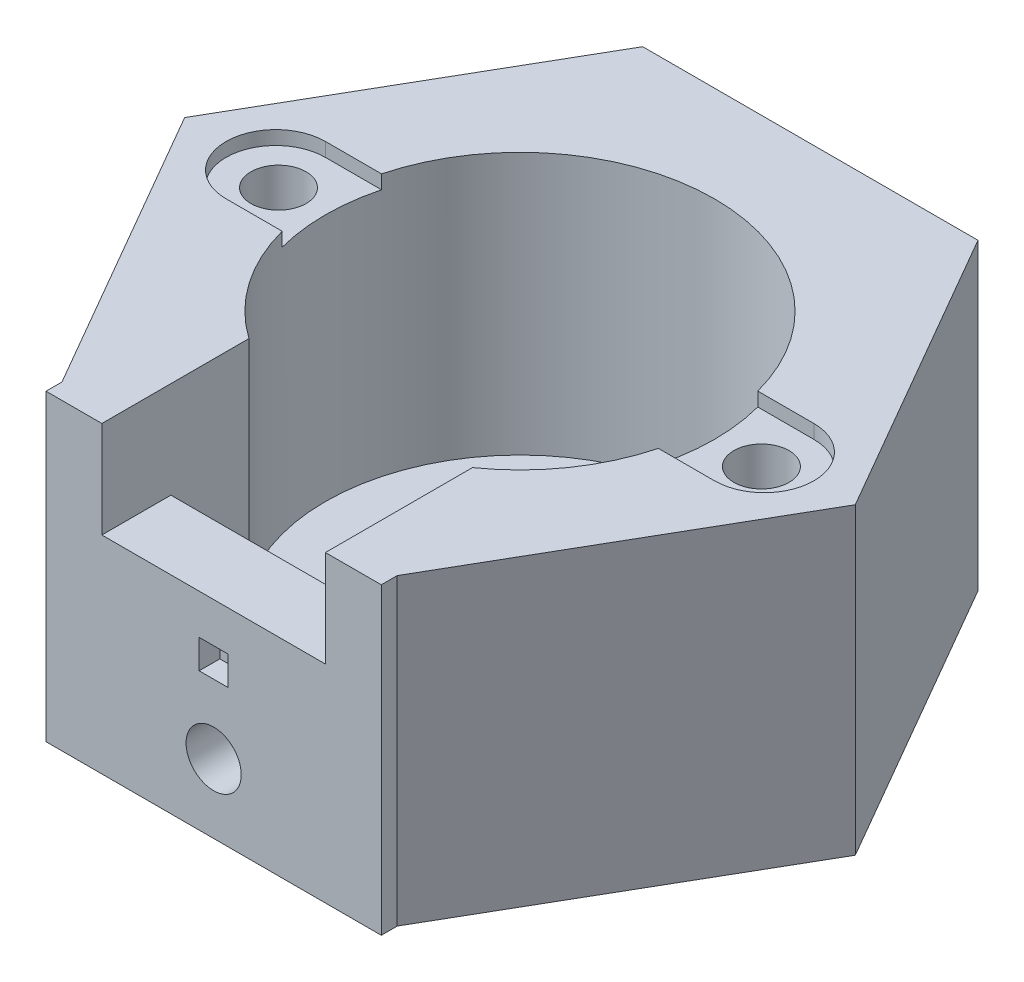
SolidWorks part; units mm, degrees
ref_plane "Front Plane" through (0, 0, 0) normal (0, 0, 1) x (1, 0, 0)
ref_plane "Top Plane" through (0, 0, 0) normal (0, 1, 0) x (1, 0, 0)
ref_plane "Right Plane" through (0, 0, 0) normal (1, 0, 0) x (0, 0, -1)
sketch "Sketch1" plane through (0, 0, 0) normal (0, 1, 0) x (1, 0, 0)
  line L0 (-33.6669, 0) -> (32.8036, 0) construction
  line L1 (0, 37.5104) -> (0, -35.9484) construction
  line L2 (-17.7, 3.6) -> (-13.6327, 3.6)
  line L3 (-17.7, -3.6) -> (-13.6327, -3.6)
  line L4 (13.6327, 3.6) -> (17.7, 3.6)
  line L5 (24.3, 0) -> (12.15, 21.0444)
  line L6 (12.15, 21.0444) -> (-12.15, 21.0444)
  line L7 (-12.15, 21.0444) -> (-24.3, 0)
  line L8 (-24.3, 0) -> (-12.15, -21.0444)
  line L9 (-12.15, -21.0444) -> (12.15, -21.0444)
  line L10 (12.15, -21.0444) -> (24.3, 0)
  line L12 (-8.1, -11.5412) -> (-8.1, -22.2)
  line L13 (-8.1, -22.2) -> (8.1, -22.2)
  line L14 (8.1, -11.5412) -> (8.1, -22.2)
  line L19 (13.6327, -3.6) -> (17.7, -3.6)
  line L20 (-8.1, -17.2) -> (8.1, -17.2)
  line L22 (-12.15, -22.2) -> (12.15, -22.2)
  line L23 (-12.15, -22.2) -> (-12.15, -21.0444)
  line L24 (-12.15, -21.0444) -> (12.15, -21.0444)
  line L25 (12.15, -22.2) -> (12.15, -21.0444)
  circle A0 centre (0, 0) radius 14.1
  arc A1 (17.7, -3.6) -> (17.7, 3.6) centre (17.7, 0) ccw
  arc A2 (-17.7, -3.6) -> (-17.7, 3.6) centre (-17.7, 0) cw
  circle A5 centre (0, 0) radius 21.0444 construction
  circle A6 centre (17.5, 0) radius 2
  circle A7 centre (-17.5, 0) radius 2
  point P38 (0, 0)
  point P39 (0, 0)
  point P40 (0, 0)
  point P41 (0, 0)
  point P42 (0, 0)
  point P43 (8.1, -21.0444)
  dimension "D1" = 28.2
  dimension "D2" = 7.2
  dimension "D3" = 4
  dimension "D5" = 3
  dimension "D7" = 5
  dimension "D4" = 35.4
  dimension "D6" = 16.2
  dimension "D9" = 35
  dimension "D10" = 17.2
extrude "Boss-Extrude12" add sketch "Sketch1" along normal blind 22 contours L3 A2 L2 A0 L4 A1 L19 L14 L9 L10 L5 L6 L7 L8 L12 region at (-21.9429, 0, 0)
extrude "Boss-Extrude13" add sketch "Sketch1<14>" along normal blind 21 contours L19 A1 L4 A0 A6 | A2 L3 A0 L2 A7 region at (-15.6663, 0, -3.4948) region at (15.6663, 0, -3.4948)
sketch "Sketch1<14>" plane through (0, 0, 0) normal (0, 1, 0) x (1, 0, 0) same geometry as "Sketch1"
extrude "Boss-Extrude14" add sketch "Sketch1<15>" along normal blind 3 contours A0 region at (0, 0, 0)
sketch "Sketch1<15>" plane through (0, 0, 0) normal (0, 1, 0) x (1, 0, 0) same geometry as "Sketch1"
extrude "Boss-Extrude15" add sketch "Sketch1<16>" along normal blind 3 contours A0 L12 L20 L14 region at (0, 0, 15.1683)
sketch "Sketch1<16>" plane through (0, 0, 0) normal (0, 1, 0) x (1, 0, 0) same geometry as "Sketch1"
extrude "Boss-Extrude16" add sketch "Sketch1<17>" along normal blind 15 contours L20 L12 L9 L14 region at (0, 0, 19.1222)
sketch "Sketch1<17>" plane through (0, 0, 0) normal (0, 1, 0) x (1, 0, 0) same geometry as "Sketch1"
extrude "Boss-Extrude17" add sketch "Sketch1<18>" along normal blind 18 contours A6 | A7 region at (17.5, 0, 0) region at (-17.5, 0, 0)
sketch "Sketch1<18>" plane through (0, 0, 0) normal (0, 1, 0) x (1, 0, 0) same geometry as "Sketch1"
extrude "Boss-Extrude18" add sketch "Sketch1<19>" along normal blind 22 contours L23 L22 L12 L9 | L22 L25 L9 L14 region at (-10.125, 0, 21.6222) region at (10.125, 0, 21.6222)
sketch "Sketch1<19>" plane through (0, 0, 0) normal (0, 1, 0) x (1, 0, 0) same geometry as "Sketch1"
extrude "Boss-Extrude19" add sketch "Sketch1<20>" along normal blind 15 contours L14 L9 L12 L13 region at (0, 0, 21.6222)
sketch "Sketch1<20>" plane through (0, 0, 0) normal (0, 1, 0) x (1, 0, 0) same geometry as "Sketch1"
sketch "Sketch10" plane through (0, 0, 22.2) normal (0, 0, 1) x (1, 0, 0)
  line L0 (0, 36.7435) -> (0, -17.2864) construction
  line L2 (-12.15, 0) -> (12.15, 0) construction
  line L3 (-1.05, 12.1) -> (1.05, 12.1)
  line L4 (-1.05, 12.1) -> (-1.05, 10)
  line L5 (-1.05, 10) -> (1.05, 10)
  line L6 (1.05, 12.1) -> (1.05, 10)
  circle A0 centre (0, 5) radius 2
  dimension "D1" = 4
  dimension "D2" = 3
  dimension "D3" = 3
  dimension "D4" = 2.1
  dimension "D5" = 2.1
extrude "Cut-Extrude6" cut sketch "Sketch10" against normal blind 3 contours A0
extrude "Cut-Extrude7" cut sketch "Sketch10<10>" against normal blind 1.5 contours L5 L6 L3 L4
sketch "Sketch10<10>" plane through (0, 0, 22.2) normal (0, 0, 1) x (1, 0, 0) same geometry as "Sketch10"
